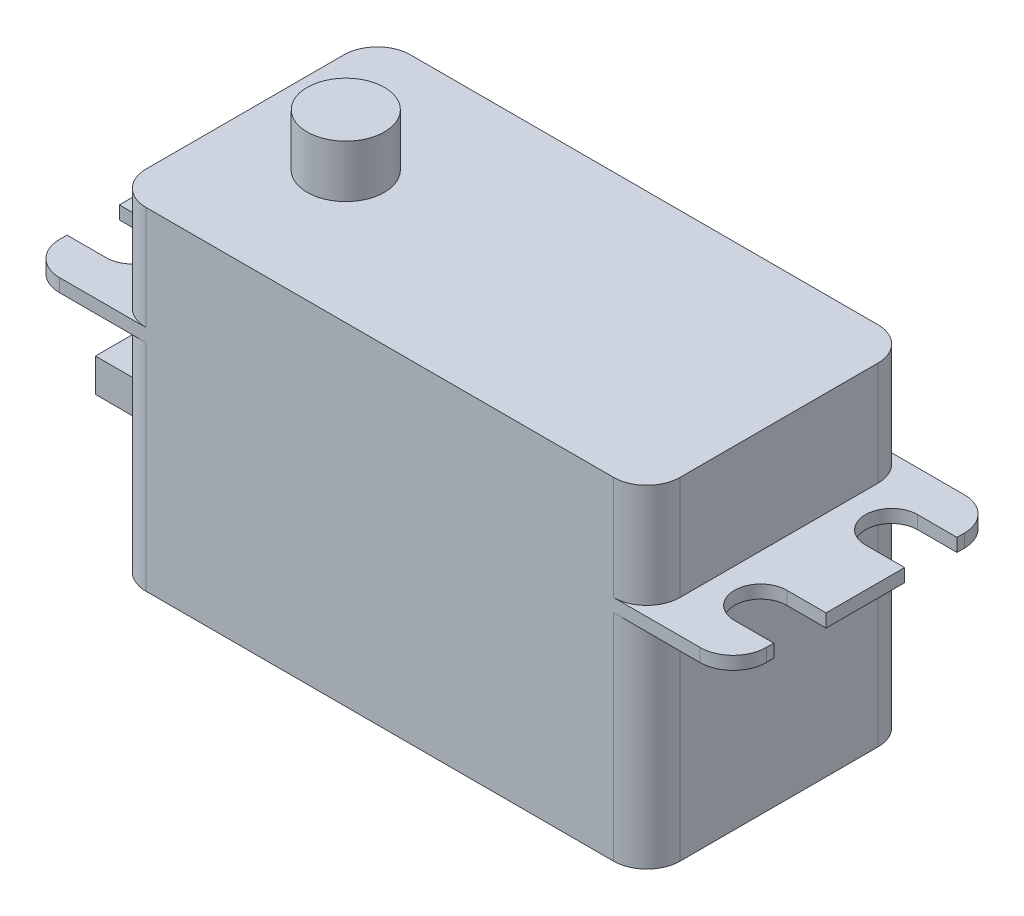
SolidWorks part; units mm, degrees
ref_plane "Front Plane" through (0, 0, 0) normal (0, 0, 1) x (1, 0, 0)
ref_plane "Top Plane" through (0, 0, 0) normal (0, 1, 0) x (1, 0, 0)
ref_plane "Right Plane" through (0, 0, 0) normal (1, 0, 0) x (0, 0, -1)
sketch "Sketch1" plane through (0, 0, 0) normal (0, 1, 0) x (1, 0, 0)
  line L0 (-16.17, 0) -> (16.17, 0) construction
  line L1 (-24.46, -10.1) -> (24.46, -10.1)
  line L2 (-27, -7.56) -> (-27, 7.56)
  line L3 (-24.46, 10.1) -> (24.46, 10.1)
  line L4 (27, -7.56) -> (27, 7.56)
  line L5 (-27, -10.1) -> (27, 10.1) construction
  line L6 (-27, 10.1) -> (27, -10.1) construction
  line L7 (0, -11.11) -> (0, 11.11) construction
  line L8 (24, 3) -> (27, 3)
  line L9 (24, 7) -> (27, 7)
  line L10 (27, 7) -> (27, 3)
  line L11 (24, -3) -> (27, -3)
  line L12 (24, -7) -> (27, -7)
  line L13 (27, -7) -> (27, -3)
  line L14 (-24, 7) -> (-27, 7)
  line L15 (-24, 3) -> (-27, 3)
  line L16 (-27, 3) -> (-27, 7)
  line L17 (-24, -7) -> (-27, -7)
  line L18 (-24, -3) -> (-27, -3)
  line L19 (-27, -3) -> (-27, -7)
  arc A0 (24, 7) -> (24, 3) centre (24, 5) ccw
  arc A1 (24, -7) -> (24, -3) centre (24, -5) cw
  arc A2 (-24, -7) -> (-24, -3) centre (-24, -5) ccw
  arc A3 (-24, 7) -> (-24, 3) centre (-24, 5) cw
  arc A4 (-24.46, -10.1) -> (-27, -7.56) centre (-24.46, -7.56) cw
  arc A5 (24.46, -10.1) -> (27, -7.56) centre (24.46, -7.56) ccw
  arc A6 (24.46, 10.1) -> (27, 7.56) centre (24.46, 7.56) cw
  arc A7 (-27, 7.56) -> (-24.46, 10.1) centre (-24.46, 7.56) cw
  point P0 (0, 0)
  dimension "D3" = 4
  dimension "D6" = 2.54
  dimension "D1" = 54
  dimension "D2" = 20.2
  dimension "D4" = 48
  dimension "D5" = 10
extrude "Boss-Extrude1" add sketch "Sketch1" along normal blind 1 contours A7 L2 L14 A3 L15 L18 A2 L17 A4 L1 A5 L4 L12 A1 L11 L8 A0 L9 A6 L3 region at (0, 0, 0)
sketch "Sketch3" plane through (0, 1, 0) normal (0, 1, 0) x (1, 0, 0)
  line L1 (-17.86, -10.1) -> (17.86, -10.1)
  line L2 (-20.4, -7.56) -> (-20.4, 7.56)
  line L3 (-17.86, 10.1) -> (17.86, 10.1)
  line L4 (20.4, -7.56) -> (20.4, 7.56)
  line L5 (-20.4, -10.1) -> (20.4, 10.1) construction
  line L6 (-20.4, 10.1) -> (20.4, -10.1) construction
  arc A0 (-17.86, -10.1) -> (-20.4, -7.56) centre (-17.86, -7.56) cw
  arc A1 (17.86, -10.1) -> (20.4, -7.56) centre (17.86, -7.56) ccw
  arc A2 (17.86, 10.1) -> (20.4, 7.56) centre (17.86, 7.56) cw
  arc A3 (-20.4, 7.56) -> (-17.86, 10.1) centre (-17.86, 7.56) cw
  point P0 (0, 0)
  dimension "D3" = 2.54
  dimension "D1" = 40.8
  dimension "D2" = 20.2
extrude "Boss-Extrude2" add sketch "Sketch3" along normal blind 7.95
sketch "Sketch4" plane through (0, 0, 0) normal (0, -1, 0) x (1, 0, 0)
  line L1 (-17.86, -10.1) -> (17.86, -10.1)
  line L2 (-20.4, -7.56) -> (-20.4, 7.56)
  line L3 (-17.86, 10.1) -> (17.86, 10.1)
  line L4 (20.4, -7.56) -> (20.4, 7.56)
  line L5 (-20.4, -10.1) -> (20.4, 10.1) construction
  line L6 (-20.4, 10.1) -> (20.4, -10.1) construction
  arc A0 (-17.86, -10.1) -> (-20.4, -7.56) centre (-17.86, -7.56) cw
  arc A1 (17.86, -10.1) -> (20.4, -7.56) centre (17.86, -7.56) ccw
  arc A2 (17.86, 10.1) -> (20.4, 7.56) centre (17.86, 7.56) cw
  arc A3 (-20.4, 7.56) -> (-17.86, 10.1) centre (-17.86, 7.56) cw
  point P0 (0, 0)
  dimension "D3" = 2.54
  dimension "D1" = 20.2
  dimension "D2" = 40.8
extrude "Boss-Extrude3" add sketch "Sketch4" along normal blind 16.45
sketch "Sketch5" plane through (-20.4, 0, 0) normal (-1, 0, 0) x (0, 0, 1)
  line L0 (-0.8843, -9.5287) -> (-0.8843, -11.2259)
  line L1 (-3.81, -11.6473) -> (3.81, -11.6473)
  line L2 (-3.81, -11.6473) -> (-3.81, -9.1073)
  line L3 (-3.81, -9.1073) -> (3.81, -9.1073)
  line L4 (3.81, -11.6473) -> (3.81, -9.1073)
  line L5 (-3.4243, -9.5287) -> (-1.6557, -9.5287)
  line L6 (-3.4243, -9.5287) -> (-3.4243, -11.2259)
  line L7 (-3.4243, -11.2259) -> (-1.6557, -11.2259)
  line L8 (-1.6557, -9.5287) -> (-1.6557, -11.2259)
  line L9 (-0.8843, -9.5287) -> (0.8843, -9.5287)
  line L10 (0.8843, -9.5287) -> (0.8843, -11.2259)
  line L11 (-0.8843, -11.2259) -> (0.8843, -11.2259)
  line L12 (1.6557, -9.5287) -> (1.6557, -11.2259)
  line L13 (1.6557, -9.5287) -> (3.4243, -9.5287)
  line L14 (3.4243, -9.5287) -> (3.4243, -11.2259)
  line L15 (1.6557, -11.2259) -> (3.4243, -11.2259)
  point P8 (0, -11.6473)
  point P18 (-3.4243, -10.3773)
  point P19 (-3.81, -10.3773)
  point P20 (0, -11.2259)
  dimension "D2" = 2.54
  dimension "D3" = 2.54
  dimension "D4" = 7.62
  dimension "D1" = 3
extrude "Boss-Extrude4" add sketch "Sketch5" along normal blind 7.62
sketch "Sketch6" plane through (0, 8.95, 0) normal (0, 1, 0) x (1, 0, 0)
  circle A0 centre (-12.7, 0) radius 2.95
  dimension "D1" = 5.9
  dimension "D2" = 12.7
extrude "Boss-Extrude5" add sketch "Sketch6" along normal blind 4
other "CPoint1" parameters "Diameter"=25.4, "StubLength"=38.1
ref_axis "Axis1" through (-38.02, -11.2259, -3.4243) along (1, 0, 0)
other "CPoint2" parameters "Diameter"=25.4, "StubLength"=38.1
ref_axis "Axis2" through (-38.02, -11.2259, -0.8843) along (1, 0, 0)
other "CPoint3" parameters "Diameter"=25.4, "StubLength"=38.1
ref_axis "Axis3" through (-38.02, -11.2259, 1.6557) along (1, 0, 0)
equation "\"Bodytube_OD\" = 6.17in"
equation "\"Bodytube_ID\" = 5.998in"
equation "\"Motor_OD\" = 4in"
equation "\"Fwd_Tube_Length\" = 40in"
equation "\"Mid_Tube_Length\" = 1in"
equation "\"Aft_Section_Length\"= 39in"
equation "\"AB_Coupler_OD_Length\"= 1in"
equation "\"AB_Coupling_Section_Length\"= 0.375in"
equation "\"AB_Coupler_Length\"= \"AB_Coupler_OD_Length\" + \"AB_Coupling_Section_Length\" * 2"
equation "\"Cutout_Angle\" = 80"
equation "\"AB_Paddle_Height\" = 0.375in"
equation "\"AB_Coupler_Num_Screws\"= 4"
equation "\"Num_Cutouts\" = 3"
equation "\"AB_Coupler_OD\"= 6.17in"
equation "\"AB_Coupler_ID\"= 5.75in"
equation "\"AB_Coupler_Surface_Diameter\"= 5.998in"
equation "\"AB_Coupling_Screw_Diameter\"= 0.1065in"
equation "\"AB_Central_Bushing_Length\" = .4724in"
equation "\"Lead_Screw_Dist\" = 3.4in"
equation "\"Lead_Screw_Diam\" = 0.386in"
equation "\"Paddle_Pin_Offset\" = .25in"
equation "\"Paddle_Pin_Radius\" = 2.25in"
equation "\"Paddle_Gear_OD\" = 3.2in"
equation "\"Drive_Gear_OD\" = 1.7in"
equation "\"Fwd_BKHD_From_Top\" = 18in"
equation "\"Fin_Thickness\"= .118in"
equation "\"Guiderail_Cutout_Diameter\"= 1.5in"
equation "\"DB9_Hole_Dist\" = 25mm"
equation "\"Airbrakes_Wire_Hole_Dia\" = .25in"
equation "\"Airbrakes_Wire_Hole_Dist\" = 1.1in"
equation "\"Servo_Gear_Offset\" = 0.5in"
equation "\"D2@Sketch6\"=\"Servo_Gear_Offset\""
